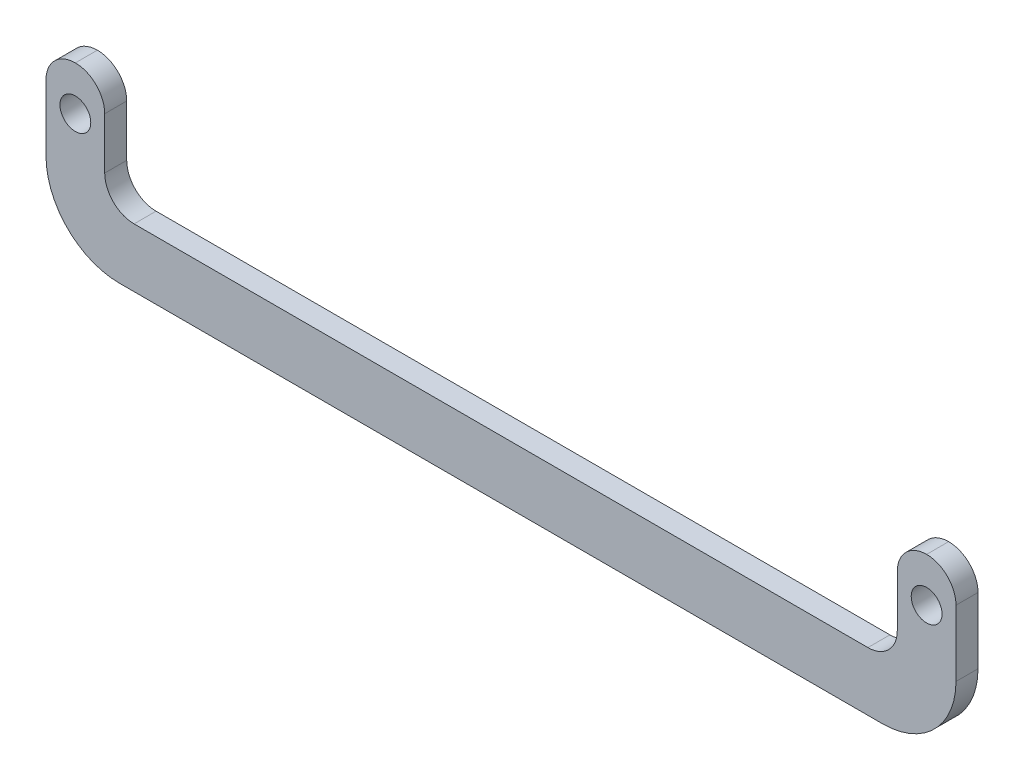
SolidWorks part; units mm, degrees
material "5052-O"
ref_plane "前基準面" through (0, 0, 0) normal (0, 0, 1) x (1, 0, 0)
ref_plane "上基準面" through (0, 0, 0) normal (0, 1, 0) x (1, 0, 0)
ref_plane "右基準面" through (0, 0, 0) normal (1, 0, 0) x (0, 0, -1)
sketch "草圖1" plane through (0, 0, 0) normal (0, 0, 1) x (1, 0, 0)
  line L1 (-62, -4) -> (62, -4)
  line L2 (-62, -4) -> (-62, 4)
  line L3 (-62, 4) -> (62, 4)
  line L4 (62, -4) -> (62, 4)
  line L5 (-62, -4) -> (62, 4) construction
  line L6 (-62, 4) -> (62, -4) construction
  point P0 (0, 0)
  dimension "D1" = 124
  dimension "D2" = 8
extrude "填料-伸長1" add sketch "草圖1" along normal blind 3
sketch "草圖2" plane through (0, 0, 3) normal (0, 0, 1) x (1, 0, 0)
  line L1 (-62, -4) -> (-54, -4)
  line L2 (-62, -4) -> (-62, 19)
  line L3 (-62, 19) -> (-54, 19)
  line L4 (-54, -4) -> (-54, 19)
  dimension "D1" = 8
  dimension "D2" = 23
extrude "填料-伸長2" add sketch "草圖2" against normal blind 3
sketch "草圖3" plane through (0, 0, 3) normal (0, 0, 1) x (1, 0, 0)
  line L0 (-54, 19) -> (-62, 19) construction
  line L1 (-58, 19) -> (-58, -4) construction
  line L2 (-62, -4) -> (62, -4) construction
  circle A0 centre (-58, 13) radius 2.1
  dimension "D1" = 4.2
  dimension "D2" = 6
extrude "除料-伸長1" cut sketch "草圖3" against normal through all
mirror "鏡射1" about plane through (0, 0, 0) normal (1, 0, 0) of "除料-伸長1", "填料-伸長2"
fillet "圓角1" radius 10 2 edges at (62, -4, 1.5) (-62, -4, 1.5)
fillet "圓角2" radius 4 6 edges at (-54, 4, 1.5) (54, 4, 1.5) (62, 19, 1.5) (54, 19, 1.5) (-54, 19, 1.5) (-62, 19, 1.5)
